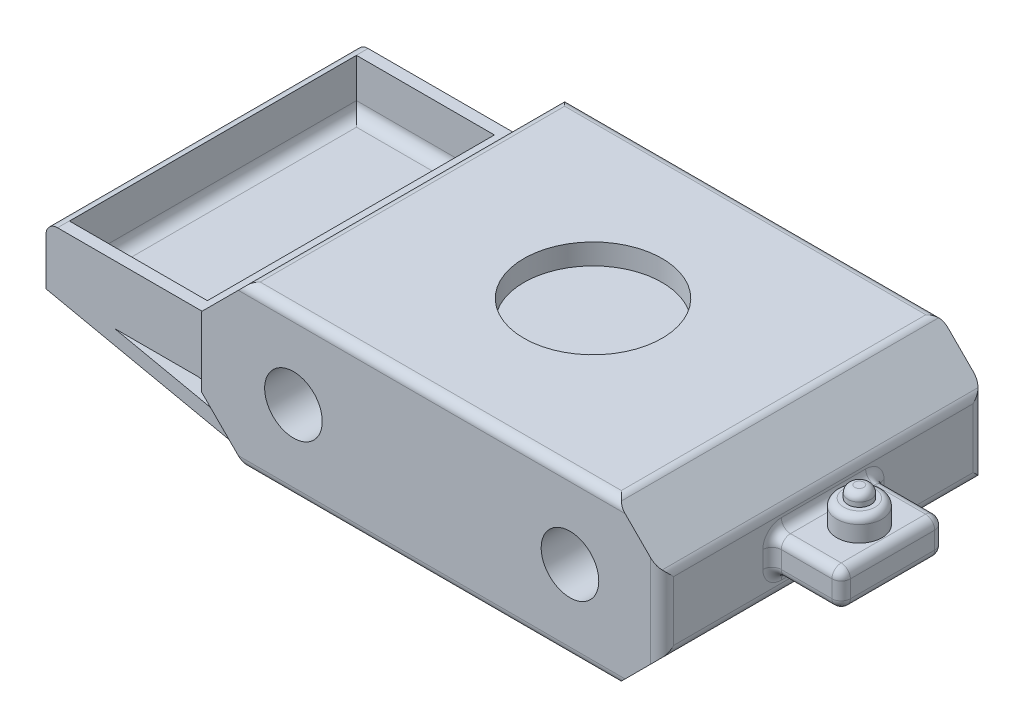
SolidWorks part; units mm, degrees
material "ABS"
ref_plane "Front Plane" through (0, 0, 0) normal (0, 0, 1) x (1, 0, 0)
ref_plane "Top Plane" through (0, 0, 0) normal (0, 1, 0) x (1, 0, 0)
ref_plane "Right Plane" through (0, 0, 0) normal (1, 0, 0) x (0, 0, -1)
sketch "Sketch3" plane through (0, 0, 0) normal (1, 0, 0) x (0, 0, -1)
  line L1 (-177.8, 88.9) -> (177.8, 88.9)
  line L2 (-177.8, 88.9) -> (-177.8, -88.9)
  line L3 (-177.8, -88.9) -> (177.8, -88.9)
  line L4 (177.8, 88.9) -> (177.8, -88.9)
  line L5 (-177.8, 88.9) -> (177.8, -88.9) construction
  line L6 (-177.8, -88.9) -> (177.8, 88.9) construction
  point P0 (0, 0)
  dimension "D1" = 355.6
  dimension "D2" = 177.8
extrude "Boss-Extrude1" add sketch "Sketch3" along normal blind 508
sketch "Sketch4" plane through (0, 0, 177.8) normal (0, 0, 1) x (1, 0, 0)
  circle A0 centre (101.6, 0) radius 31.75
  point P10 (355.6, 0)
  dimension "D1" = 63.5
extrude "Cut-Extrude1" cut sketch "Sketch4" against normal through all both and the other way through all contours A0
ref_plane "Plane1" through (254, 0, 0) normal (-1, 0, 0) x (0, 0, 1)
mirror "Mirror1" about plane through (254, 0, 0) normal (-1, 0, 0) of "Cut-Extrude1"
fillet "Chamfer1" radius 50.8 1 edges at (0, 88.9, 0) type face fillet profile chamfer first side face at (254, 88.9, 0) second side face at (0, 0, 0)
fillet "Chamfer2" radius 50.8 1 edges at (0, -88.9, 0) type face fillet profile chamfer first side face at (0, -25.4, 0) second side face at (254, -88.9, 0)
fillet "Chamfer3" radius 50.8 1 edges at (508, 88.9, 0) type face fillet profile chamfer first side face at (279.4, 88.9, 0) second side face at (508, 0, 0)
fillet "Chamfer4" radius 50.8 1 edges at (508, -88.9, 0) type face fillet profile chamfer first side face at (279.4, -88.9, 0) second side face at (508, -25.4, 0)
fillet "Fillet1" radius 10 8 edges at (50.8, -88.9, 0) (254, -88.9, 177.8) (457.2, -88.9, 0) (254, -88.9, -177.8) (50.8, 88.9, 0) (254, 88.9, -177.8) (457.2, 88.9, 0) (254, 88.9, 177.8)
sketch "Sketch5" plane through (0, 88.9, 0) normal (0, 1, 0) x (1, 0, 0)
  line L0 (254, 41.91) -> (254, -41.91) construction
  circle A0 centre (254, 0) radius 76.2
  dimension "D1" = 152.4
extrude "Cut-Extrude2" cut sketch "Sketch5" against normal blind 22.86
sketch "Sketch7" plane through (0, 0, 0) normal (-1, 0, 0) x (0, 0, 1)
  line L1 (-171.1619, 32.3443) -> (171.1619, 32.3443)
  line L2 (-171.1619, 32.3443) -> (-171.1619, -32.3443)
  line L3 (-171.1619, -32.3443) -> (171.1619, -32.3443)
  line L4 (171.1619, 32.3443) -> (171.1619, -32.3443)
  line L5 (-171.1619, 32.3443) -> (171.1619, -32.3443) construction
  line L6 (-171.1619, -32.3443) -> (171.1619, 32.3443) construction
  point P0 (0, 0)
extrude "Boss-Extrude3" add sketch "Sketch7" along normal blind 177.8
sketch "Sketch8" plane through (0, 32.3443, 0) normal (0, 1, 0) x (1, 0, 0)
  line L4 (-164.9087, 158.1843) -> (-12.8913, 158.1843)
  line L5 (-164.9087, 158.1843) -> (-164.9087, -158.1843)
  line L6 (-164.9087, -158.1843) -> (-12.8913, -158.1843)
  line L7 (-12.8913, 158.1843) -> (-12.8913, -158.1843)
  line L8 (-164.9087, 158.1843) -> (-12.8913, -158.1843) construction
  line L9 (-164.9087, -158.1843) -> (-12.8913, 158.1843) construction
  point P6 (-88.9, 0)
extrude "Cut-Extrude3" cut sketch "Sketch8" against normal blind 55.88
sketch "Sketch10" plane through (0, 0, 171.1619) normal (0, 0, 1) x (1, 0, 0)
  line L0 (-177.8, -32.3443) -> (40.8, -78.9)
  line L1 (40.8, -78.9) -> (20.4, -58.5)
  line L2 (0, -38.1) -> (40.8, -78.9) construction
  line L3 (20.4, -58.5) -> (-102.4127, -32.3443)
  line L4 (-177.8, -32.3443) -> (0, -32.3443) construction
  line L5 (-102.4127, -32.3443) -> (-177.8, -32.3443)
extrude "Boss-Extrude5" add sketch "Sketch10" against normal blind 55.88
mirror "Mirror2" about plane through (0, 0, 0) normal (0, 0, 1) of "Boss-Extrude5"
sketch "Sketch11" plane through (508, 0, 0) normal (1, 0, 0) x (0, 0, -1)
  line L1 (-56.6413, 19.6542) -> (56.6413, 19.6542)
  line L2 (-56.6413, 19.6542) -> (-56.6413, -19.6542)
  line L3 (-56.6413, -19.6542) -> (56.6413, -19.6542)
  line L4 (56.6413, 19.6542) -> (56.6413, -19.6542)
  line L5 (-56.6413, 19.6542) -> (56.6413, -19.6542) construction
  line L6 (-56.6413, -19.6542) -> (56.6413, 19.6542) construction
  point P0 (0, 0)
extrude "Boss-Extrude6" add sketch "Sketch11" along normal blind 76.2
fillet "Fillet2" radius 10.16 12 edges at (508, -19.6542, 0) (508, 19.6542, 0) (546.1, 19.6542, 56.6413) (546.1, -19.6542, 56.6413) (508, 0, 56.6413) (546.1, -19.6542, -56.6413) (546.1, 19.6542, -56.6413) (508, 0, -56.6413) (584.2, -19.6542, 0) (584.2, 0, 56.6413) (584.2, 19.6542, 0) (584.2, 0, -56.6413)
fillet "Fillet3" radius 12.7 4 edges at (508, 38.1, 0) (508, 0, -177.8) (508, -38.1, 0) (508, 0, 177.8)
fillet "Fillet4" radius 12.7 5 edges at (-88.9, -23.5357, 158.1843) (-88.9, -23.5357, -158.1843) (-164.9087, -23.5357, 0) (0, -32.3443, 0) (-12.8913, -23.5357, 0)
fillet "Fillet5" radius 12.7 1 edges at (-177.8, 32.3443, 0)
sketch "Sketch12" plane through (0, 19.6542, 0) normal (0, 1, 0) x (1, 0, 0)
  circle A0 centre (547.6076, 0) radius 24.9488
extrude "Boss-Extrude7" add sketch "Sketch12" along normal blind 25.4
fillet "Fillet6" radius 7.62 1 edges at (547.6076, 45.0542, 24.9488)
sketch "Sketch13" plane through (0, 45.0542, 0) normal (0, 1, 0) x (1, 0, 0)
  circle A0 centre (547.6076, 0) radius 12.609
extrude "Boss-Extrude8" add sketch "Sketch13" along normal blind 12.7
fillet "Fillet7" radius 7.62 1 edges at (547.6076, 57.7542, 12.609)
